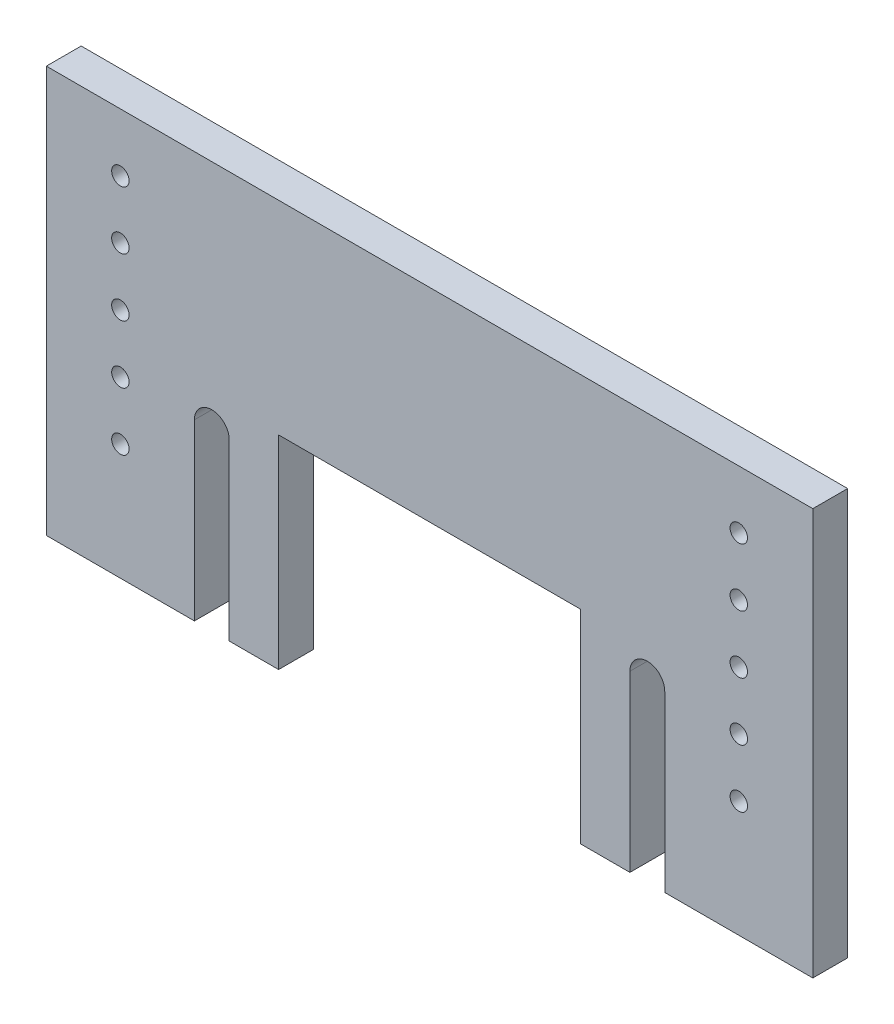
SolidWorks part; units mm, degrees
material "Balsa"
ref_plane "Plano frontal" through (0, 0, 0) normal (0, 0, 1) x (1, 0, 0)
ref_plane "Plano superior" through (0, 0, 0) normal (0, 1, 0) x (1, 0, 0)
ref_plane "Plano direito" through (0, 0, 0) normal (1, 0, 0) x (0, 0, -1)
sketch "Esboço1" plane through (0, 0, 0) normal (0, 0, 1) x (1, 0, 0)
  line L0 (-66, -35) -> (-40.5, -35)
  line L1 (40.5, -35) -> (66, -35)
  line L2 (66, -35) -> (66, 35)
  line L3 (66, 35) -> (-66, 35)
  line L4 (-66, -35) -> (-66, 35)
  line L5 (66, -35) -> (-66, 35) construction
  line L6 (66, 35) -> (-66, -35) construction
  line L7 (34.5, -35) -> (26, -35)
  line L8 (34.5, -5) -> (34.5, -35)
  line L9 (40.5, -5) -> (40.5, -35)
  line L10 (-40.5, -5) -> (-40.5, -35)
  line L11 (-34.5, -5) -> (-34.5, -35)
  line L12 (-26, -35) -> (-34.5, -35)
  line L13 (0, 0) -> (0, -26.3908) construction
  line L14 (26, -35) -> (26, 0)
  line L15 (26, 0) -> (-26, 0)
  line L16 (-26, -35) -> (-26, 0)
  arc A0 (-34.5, -5) -> (-40.5, -5) centre (-37.5, -5) ccw
  arc A1 (40.5, -5) -> (34.5, -5) centre (37.5, -5) ccw
  circle A2 centre (-53.25, -5) radius 1.5
  circle A3 centre (-53.25, -15) radius 1.5
  circle A4 centre (-53.25, 15) radius 1.5
  circle A5 centre (-53.25, 25) radius 1.5
  circle A6 centre (-53.25, 5) radius 1.5
  circle A7 centre (53.25, 5) radius 1.5
  circle A8 centre (53.25, 25) radius 1.5
  circle A9 centre (53.25, 15) radius 1.5
  circle A10 centre (53.25, -15) radius 1.5
  circle A11 centre (53.25, -5) radius 1.5
  point P0 (0, 0)
  point P28 (0, 0)
  point P32 (-53.25, -35)
  dimension "D1" = 8.5
  dimension "D15" = 3
  dimension "D5" = 10
  dimension "D2" = 75
  dimension "D3" = 35
  dimension "D4" = 25.5
  dimension "D6" = 6
  dimension "D7" = 30
  dimension "D8" = 132
  dimension "D9" = 10
  dimension "D10" = 70
  dimension "D14" = 10
  dimension "D16" = 10
  dimension "D17" = 10
extrude "Ressalto-extrusão1" add sketch "Esboço1" along normal blind 6
